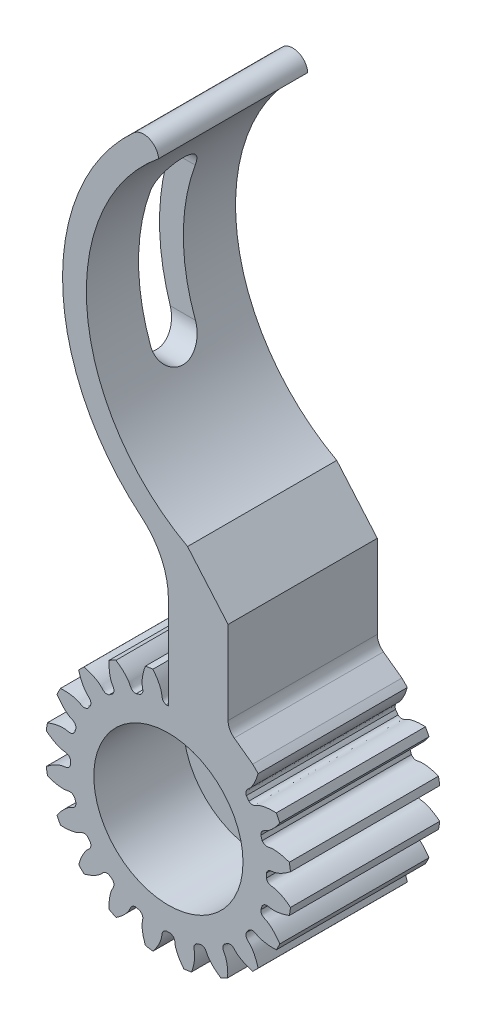
SolidWorks part; units mm, degrees
material "聚脂树脂"
ref_plane "前视基准面" through (0, 0, 0) normal (0, 0, 1) x (1, 0, 0)
ref_plane "上视基准面" through (0, 0, 0) normal (0, 1, 0) x (1, 0, 0)
ref_plane "右视基准面" through (0, 0, 0) normal (1, 0, 0) x (0, 0, -1)
other "Configuration Table"
sketch "草图1" plane through (0, 0, 0) normal (0, 0, 1) x (1, 0, 0)
  circle A0 centre (0, 0) radius 16.5
extrude "凸台-拉伸1" add sketch "草图1" along normal blind 20
ref_axis "基准轴1" through (0, 0, -1.5) along (0, 0, 1)
sketch "草图2" plane through (0, 0, 0) normal (0, 0, 1) x (1, 0, 0)
  line L0 (0, 0) -> (0, 16.5) construction
  circle A0 centre (0, 0) radius 16.5 construction
  arc A1 (0.29, 13.1218) -> (-0.29, 13.1218) centre (0, 0) ccw
  arc A2 (4.7717, 18.7474) -> (-4.7717, 18.7474) centre (0, 0) ccw
  spline S0 degree 3 poles (0.29, 13.1218) (0.9168, 13.3402) (0.8356, 13.7807) (0.9193, 14.205) (0.9283, 14.2463) (0.9395, 14.293) (0.9529, 14.3448) (0.969, 14.4018) (0.9878, 14.4638) (1.0095, 14.5309) (1.0345, 14.6028) (1.0629, 14.6795) (1.0948, 14.7608) (1.1305, 14.8467) (1.1702, 14.9371) (1.2141, 15.0317) (1.2623, 15.1305) (1.315, 15.2334) (1.3725, 15.3401) (1.4349, 15.4506) (1.5023, 15.5646) (1.575, 15.6821) (1.653, 15.8029) (1.7366, 15.9267) (1.826, 16.0534) (1.9211, 16.1829) (2.0223, 16.3149) (2.1296, 16.4493) (2.2432, 16.5859) (2.3632, 16.7244) (2.4897, 16.8646) (2.6229, 17.0065) (2.7628, 17.1496) (2.9095, 17.2939) (3.0632, 17.4391) (3.224, 17.585) (3.3918, 17.7313) (3.567, 17.8779) (3.7493, 18.0245) (3.9391, 18.1709) (4.1363, 18.3167) (4.4122, 18.5125) (4.6259, 18.6545) (4.7717, 18.7474) knots 0 0 0 0 0.165916 0.170906 0.176664 0.183189 0.190482 0.198542 0.207371 0.216967 0.22733 0.238462 0.250361 0.263027 0.276462 0.290664 0.305634 0.321371 0.337876 0.355149 0.37319 0.391998 0.411574 0.431917 0.453028 0.474907 0.497554 0.520968 0.54515 0.570099 0.595817 0.622302 0.649554 0.677575 0.706363 0.735918 0.766242 0.797333 0.829191 0.861818 0.895212 0.929373 1 1 1 1
  spline S1 degree 3 poles (-0.29, 13.1218) (-0.9168, 13.3402) (-0.8356, 13.7807) (-0.9193, 14.205) (-0.9283, 14.2463) (-0.9395, 14.293) (-0.9529, 14.3448) (-0.969, 14.4018) (-0.9878, 14.4638) (-1.0095, 14.5309) (-1.0345, 14.6028) (-1.0629, 14.6795) (-1.0948, 14.7608) (-1.1305, 14.8467) (-1.1702, 14.9371) (-1.2141, 15.0317) (-1.2623, 15.1305) (-1.315, 15.2334) (-1.3725, 15.3401) (-1.4349, 15.4506) (-1.5023, 15.5646) (-1.575, 15.6821) (-1.653, 15.8029) (-1.7366, 15.9267) (-1.826, 16.0534) (-1.9211, 16.1829) (-2.0223, 16.3149) (-2.1296, 16.4493) (-2.2432, 16.5859) (-2.3632, 16.7244) (-2.4897, 16.8646) (-2.6229, 17.0065) (-2.7628, 17.1496) (-2.9095, 17.2939) (-3.0632, 17.4391) (-3.224, 17.585) (-3.3918, 17.7313) (-3.567, 17.8779) (-3.7493, 18.0245) (-3.9391, 18.1709) (-4.1363, 18.3167) (-4.4122, 18.5125) (-4.6259, 18.6545) (-4.7717, 18.7474) knots 0 0 0 0 0.165916 0.170906 0.176664 0.183189 0.190482 0.198542 0.207371 0.216967 0.22733 0.238462 0.250361 0.263027 0.276462 0.290664 0.305634 0.321371 0.337876 0.355149 0.37319 0.391998 0.411574 0.431917 0.453028 0.474907 0.497554 0.520968 0.54515 0.570099 0.595817 0.622302 0.649554 0.677575 0.706363 0.735918 0.766242 0.797333 0.829191 0.861818 0.895212 0.929373 1 1 1 1
extrude "切除-拉伸1" cut sketch "草图2" along normal through all
pattern_circular "阵列(圆周)1" count 20 over 360 about axis through (0, 0, -1.5) along (0, 0, 1) of "切除-拉伸1"
sketch "草图3" plane through (0, 0, 0) normal (0, 0, 1) x (1, 0, 0)
  circle A0 centre (0, 0) radius 15 construction
  dimension "Dn" = 30
sketch "草图4" plane through (0, 0, 0) normal (0, 0, -1) x (-1, 0, 0)
  line L0 (0, 0) -> (67.6919, 0) construction
  line L1 (0, 13.125) -> (0, 76.7697) construction
  line L2 (-15, 0) -> (-15, 67.6903) construction
  line L6 (-7.9502, 14.4584) -> (-11.294, 12.029)
  line L7 (-8, 0) -> (-8, 30.72)
  line L8 (0, 30.72) -> (0, 0)
  line L9 (1.261, 80) -> (1.32, 76)
  line L10 (-8, 0) -> (0, 0)
  circle A2 centre (-15, 55.76) radius 26 construction
  arc A4 (-8, 30.72) -> (1.32, 76) centre (-15, 55.76) ccw
  arc A6 (0.29, 13.1218) -> (-0.29, 13.1218) centre (0, 0) ccw construction
  arc A7 (-2.0665, 16.3701) -> (-3.0932, 16.2075) centre (0, 0) ccw construction
  arc A8 (-3.7791, 12.5692) -> (-4.3306, 12.39) centre (0, 0) ccw construction
  arc A9 (-7.024, 14.9303) -> (-7.9502, 14.4584) centre (0, 0) ccw construction
  arc A10 (0, 13.125) -> (-0.29, 13.1218) centre (0, 0) ccw
  arc A11 (-2.0665, 16.3701) -> (-3.0932, 16.2075) centre (0, 0) ccw
  arc A12 (-3.7791, 12.5692) -> (-4.3306, 12.39) centre (0, 0) ccw
  arc A13 (-7.024, 14.9303) -> (-7.9502, 14.4584) centre (0, 0) ccw
  arc A14 (-7.4782, 10.7862) -> (-7.9474, 10.4453) centre (0, 0) ccw construction
  arc A15 (-7.4782, 10.7862) -> (-7.9474, 10.4453) centre (0, 0) ccw
  circle A16 centre (0, 0) radius 12.5
  circle A17 centre (-15, 55.76) radius 29.189 construction
  arc A18 (0, 30.72) -> (1.261, 80) centre (-15, 55.76) ccw
  spline S2 degree 3 poles (9636.1577, 2672.394) (-75.3968, -18.2301) (0.8601, 5.1856) (-0.9224, 14.2207) (-0.9359, 14.2793) (-0.9529, 14.3448) (-0.969, 14.4018) (-0.9951, 14.4881) (-1.0357, 14.6084) (-1.0961, 14.7664) (-1.1716, 14.9426) (-1.2638, 15.1361) (-1.3741, 15.3456) (-1.5041, 15.5702) (-1.6549, 15.8084) (-1.7965, 16.0133) (-1.9211, 16.1829) (-29.6649, 52.3852) (-347.1976, -138.1957) (9963.7292, 828.2221) knots -3.578314 -3.578314 -3.578314 -3.578314 0.165916 0.170906 0.183189 0.190482 0.198542 0.207371 0.22733 0.250361 0.276462 0.305634 0.337876 0.37319 0.411574 0.453028 0.474907 0.497554 19.082782 19.082782 19.082782 19.082782 only from (-0.29, 13.1218) to (-2.0665, 16.3701) construction
  spline S3 degree 3 poles (-9990.3457, -436.1387) (77.34, 5.961) (-2.4205, 4.666) (-3.5171, 13.8097) (-3.5224, 13.8696) (-3.5265, 13.9372) (-3.5289, 13.9963) (-3.5307, 14.0865) (-3.5293, 14.2134) (-3.5206, 14.3824) (-3.5033, 14.5733) (-3.4754, 14.7858) (-3.4352, 15.0192) (-3.381, 15.2729) (-3.3111, 15.5461) (-3.2398, 15.7847) (-3.1737, 15.9845) (12.0251, 58.9882) (372.9094, -24.1419) (-9732.0043, -2291.2756) knots -3.085746 -3.085746 -3.085746 -3.085746 0.658484 0.663474 0.675757 0.68305 0.691111 0.699939 0.719899 0.742929 0.76903 0.798202 0.830445 0.865758 0.904142 0.945597 0.967475 0.990122 19.575351 19.575351 19.575351 19.575351 only from (-3.7791, 12.5692) to (-3.0932, 16.2075) construction
  spline S4 degree 3 poles (8338.7154, 5519.3342) (-66.0732, -40.6368) (-0.7844, 5.1976) (-5.2717, 13.2396) (-5.3027, 13.2912) (-5.3391, 13.3482) (-5.3719, 13.3975) (-5.4235, 13.4715) (-5.4992, 13.5733) (-5.6055, 13.705) (-5.7318, 13.8492) (-5.8792, 14.0047) (-6.0489, 14.1699) (-6.2419, 14.3433) (-6.459, 14.5233) (-6.6569, 14.6744) (-6.8279, 14.7972) (-44.4009, 40.6543) (-287.4997, -238.7219) (9220.1348, 3866.6477) knots -3.578314 -3.578314 -3.578314 -3.578314 0.165916 0.170906 0.183189 0.190482 0.198542 0.207371 0.22733 0.250361 0.276462 0.305634 0.337876 0.37319 0.411574 0.453028 0.474907 0.497554 19.082782 19.082782 19.082782 19.082782 only from (-4.3306, 12.39) to (-7.024, 14.9303) construction
  spline S5 degree 3 poles (-0.29, 13.1218) (-0.9168, 13.3402) (-0.8356, 13.7807) (-0.9224, 14.2207) (-0.9359, 14.2793) (-0.9529, 14.3448) (-0.969, 14.4018) (-0.9951, 14.4881) (-1.0357, 14.6084) (-1.0961, 14.7664) (-1.1716, 14.9426) (-1.2638, 15.1361) (-1.3741, 15.3456) (-1.5041, 15.5702) (-1.6549, 15.8084) (-1.828, 16.0589) (-1.969, 16.2466) (-2.0515, 16.3512) (-2.0665, 16.3701) knots 0 0 0 0 0.165916 0.170906 0.183189 0.190482 0.198542 0.207371 0.22733 0.250361 0.276462 0.305634 0.337876 0.37319 0.411574 0.453028 0.497554 0.507432 0.507432 0.507432 0.507432
  spline S6 degree 3 poles (-3.7791, 12.5692) (-3.2504, 12.9706) (-3.4637, 13.3644) (-3.5171, 13.8097) (-3.5224, 13.8696) (-3.5265, 13.9372) (-3.5289, 13.9963) (-3.5307, 14.0865) (-3.5293, 14.2134) (-3.5206, 14.3824) (-3.5033, 14.5733) (-3.4754, 14.7858) (-3.4352, 15.0192) (-3.381, 15.2729) (-3.3111, 15.5461) (-3.224, 15.8378) (-3.1479, 16.0599) (-3.1017, 16.1848) (-3.0932, 16.2075) knots 0.492568 0.492568 0.492568 0.492568 0.658484 0.663474 0.675757 0.68305 0.691111 0.699939 0.719899 0.742929 0.76903 0.798202 0.830445 0.865758 0.904142 0.945597 0.990122 1 1 1 1
  spline S7 degree 3 poles (-4.3306, 12.39) (-4.9943, 12.404) (-5.0532, 12.848) (-5.2717, 13.2396) (-5.3027, 13.2912) (-5.3391, 13.3482) (-5.3719, 13.3975) (-5.4235, 13.4715) (-5.4992, 13.5733) (-5.6055, 13.705) (-5.7318, 13.8492) (-5.8792, 14.0047) (-6.0489, 14.1699) (-6.2419, 14.3433) (-6.459, 14.5233) (-6.701, 14.7081) (-6.8931, 14.843) (-7.0039, 14.9169) (-7.024, 14.9303) knots 0 0 0 0 0.165916 0.170906 0.183189 0.190482 0.198542 0.207371 0.22733 0.250361 0.276462 0.305634 0.337876 0.37319 0.411574 0.453028 0.497554 0.507432 0.507432 0.507432 0.507432
  spline S8 degree 3 poles (-9366.6091, -3501.9792) (71.7127, 29.5686) (-3.7439, 3.6897) (-7.6124, 12.047) (-7.636, 12.1023) (-7.6607, 12.1653) (-7.6812, 12.2208) (-7.7108, 12.3061) (-7.7487, 12.4272) (-7.7927, 12.5905) (-7.8352, 12.7775) (-7.8743, 12.9882) (-7.9082, 13.2226) (-7.9351, 13.4806) (-7.9531, 13.762) (-7.959, 14.011) (-7.9578, 14.2215) (-6.7918, 59.817) (362.1182, 92.275) (-8547.643, -5186.4873) knots -3.085746 -3.085746 -3.085746 -3.085746 0.658484 0.663474 0.675757 0.68305 0.691111 0.699939 0.719899 0.742929 0.76903 0.798202 0.830445 0.865758 0.904142 0.945597 0.967475 0.990122 19.575351 19.575351 19.575351 19.575351 only from (-7.4782, 10.7862) to (-7.9502, 14.4584) construction
  spline S9 degree 3 poles (6225.0215, 7826.0035) (-50.2819, -59.0656) (-2.3522, 4.7008) (-9.105, 10.9626) (-9.1503, 11.0021) (-9.2026, 11.0451) (-9.2491, 11.0817) (-9.321, 11.1362) (-9.4245, 11.2097) (-9.5662, 11.302) (-9.7309, 11.4002) (-9.9192, 11.5025) (-10.1316, 11.6072) (-10.3687, 11.7125) (-10.6308, 11.8165) (-10.8658, 11.8991) (-11.0663, 11.963) (-54.7906, 24.9439) (-199.6594, -315.8803) (7574.0095, 6526.5788) knots -3.578314 -3.578314 -3.578314 -3.578314 0.165916 0.170906 0.183189 0.190482 0.198542 0.207371 0.22733 0.250361 0.276462 0.305634 0.337876 0.37319 0.411574 0.453028 0.474907 0.497554 19.082782 19.082782 19.082782 19.082782 only from (-7.9474, 10.4453) to (-11.294, 12.029) construction
  spline S10 degree 3 poles (-7.4782, 10.7862) (-7.0995, 11.3313) (-7.424, 11.64) (-7.6124, 12.047) (-7.636, 12.1023) (-7.6607, 12.1653) (-7.6812, 12.2208) (-7.7108, 12.3061) (-7.7487, 12.4272) (-7.7927, 12.5905) (-7.8352, 12.7775) (-7.8743, 12.9882) (-7.9082, 13.2226) (-7.9351, 13.4806) (-7.9531, 13.762) (-7.9603, 14.0664) (-7.9566, 14.3011) (-7.9513, 14.4342) (-7.9502, 14.4584) knots 0.492568 0.492568 0.492568 0.492568 0.658484 0.663474 0.675757 0.68305 0.691111 0.699939 0.719899 0.742929 0.76903 0.798202 0.830445 0.865758 0.904142 0.945597 0.990122 1 1 1 1
  spline S11 degree 3 poles (-7.9474, 10.4453) (-8.5829, 10.2536) (-8.7761, 10.6576) (-9.105, 10.9626) (-9.1503, 11.0021) (-9.2026, 11.0451) (-9.2491, 11.0817) (-9.321, 11.1362) (-9.4245, 11.2097) (-9.5662, 11.302) (-9.7309, 11.4002) (-9.9192, 11.5025) (-10.1316, 11.6072) (-10.3687, 11.7125) (-10.6308, 11.8165) (-10.9181, 11.9175) (-11.1425, 11.9864) (-11.2707, 12.0225) (-11.294, 12.029) knots 0 0 0 0 0.165916 0.170906 0.183189 0.190482 0.198542 0.207371 0.22733 0.250361 0.276462 0.305634 0.337876 0.37319 0.411574 0.453028 0.497554 0.507432 0.507432 0.507432 0.507432
  dimension "D4" = 52
  dimension "D5" = 80
  dimension "D3" = 25
  dimension "D1" = 15
  dimension "D2" = 30.72
  dimension "D6" = 76
  dimension "D8" = 8
  dimension "D9" = 30.72
extrude "凸台-拉伸2" add sketch "草图4" against normal blind 20 contours S7 A12 S6 A11 S5 A10 L8 A18 L9 A4 L7 L6 A13 | S11 L7 L6 | L6 S11 A15 S10 region at (7.2884, 22.5711, 0) region at (9.051, 12.2758, 0)
fillet "圆角1" radius 10 1 edges at (0, 30.72, 10)
fillet "圆角2" radius 2 2 edges at (8, 14.4222, 10) (-1.261, 80, 10)
sketch "草图5" plane through (0, 0, 0) normal (0, 0, -1) x (-1, 0, 0)
  line L0 (0, 0) -> (47.9973, 0) construction
  line L1 (0, 0) -> (0, 54.3289) construction
sketch "草图7" plane through (0, 0, 20) normal (0, 0, 1) x (1, 0, 0)
  line L0 (0, 0) -> (42.9933, 0) construction
  line L1 (0, 0) -> (0, 51.6895) construction
  circle A0 centre (0, 0) radius 10
  dimension "D1" = 20
extrude "切除-拉伸2" cut sketch "草图7" against normal blind 12
sketch "草图8" plane through (0, 0, 8) normal (0, 0, 1) x (1, 0, 0)
  line L0 (0, 0) -> (25.4464, 0) construction
  line L1 (0, 0) -> (0, 31.9913) construction
  circle A0 centre (0, 0) radius 3.5
  circle A1 centre (0, 7) radius 1.5
  circle A2 centre (7, 0) radius 1.5
  circle A3 centre (0, -7) radius 1.5
  circle A4 centre (-7, 0) radius 1.5
  dimension "D1" = 3
  dimension "D2" = 7
  dimension "D4" = 3
  dimension "D3" = 7
  dimension "D5" = 7
extrude "切除-拉伸3" cut sketch "草图8" against normal blind 10
chamfer "倒角1" distance 5 angle 45 1 edges at (8, 30.72, 10) first distance on face at (8, 23.0806, 10)
sketch "草图10" plane through (0, 0, 0) normal (0, 0, -1) x (-1, 0, 0)
  circle A0 centre (0, 0) radius 10
  circle A1 centre (-7, 0) radius 1.5 construction
  circle A2 centre (0, -7) radius 1.5 construction
  circle A3 centre (0, 0) radius 3.5 construction
  circle A4 centre (7, 0) radius 1.5 construction
  circle A5 centre (0, 7) radius 1.5 construction
  circle A6 centre (-7, 0) radius 1.5
  circle A7 centre (0, -7) radius 1.5
  circle A8 centre (0, 0) radius 3.5
  circle A9 centre (7, 0) radius 1.5
  circle A10 centre (0, 7) radius 1.5
  dimension "D1" = 20
extrude "凸台-拉伸3" add sketch "草图10" along normal blind 2
fillet "圆角3" radius 2 1 edges at (10, 0, 0)
sketch "草图11" plane through (0, 0, 0) normal (1, 0, 0) x (0, 0, -1)
  line L0 (-10, 46.72) -> (-10, 64.72) construction
  line L1 (-13, 46.72) -> (-13, 64.72)
  line L2 (-7, 46.72) -> (-7, 64.72)
  line L3 (0, 32.9259) -> (0, 76) construction
  arc A0 (-13, 46.72) -> (-7, 46.72) centre (-10, 46.72) ccw
  arc A1 (-7, 64.72) -> (-13, 64.72) centre (-10, 64.72) ccw
  point P2 (-10, 55.72)
  dimension "D2" = 3
  dimension "D1" = 18
  dimension "D3" = 10
  dimension "D4" = 55.72
extrude "切除-拉伸4" cut sketch "草图11" against normal blind 24
